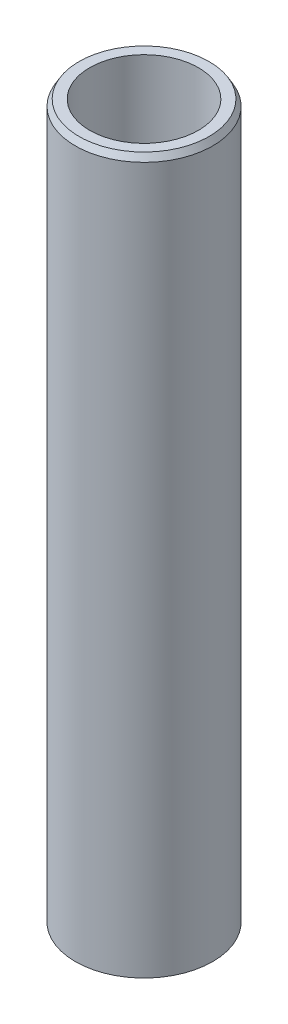
SolidWorks part; units mm, degrees
ref_plane "Front Plane" through (0, 0, 0) normal (0, 0, 1) x (1, 0, 0)
ref_plane "Top Plane" through (0, 0, 0) normal (0, 1, 0) x (1, 0, 0)
ref_plane "Right Plane" through (0, 0, 0) normal (1, 0, 0) x (0, 0, -1)
sketch "Sketch1" plane through (0, 0, 0) normal (0, 1, 0) x (1, 0, 0)
  circle A0 centre (0, 0) radius 57.5
  dimension "SHAFT_OD" = 115
extrude "Boss-Extrude1" add sketch "Sketch1" along normal blind 600
sketch "Sketch2" plane through (0, 0, 0) normal (0, 1, 0) x (1, 0, 0)
  circle A0 centre (0, 0) radius 45.5176
  dimension "BORE_D" = 91.0351
extrude "Cut-Extrude1" cut sketch "Sketch2" along normal through all
chamfer "Chamfer1" distance 5.3136 angle 30 2 edges at (0, 600, 57.5) (0, 0, 57.5) first distance on face at (0, 600, 57.5) first distance on face at (0, 0, 45.5176)
